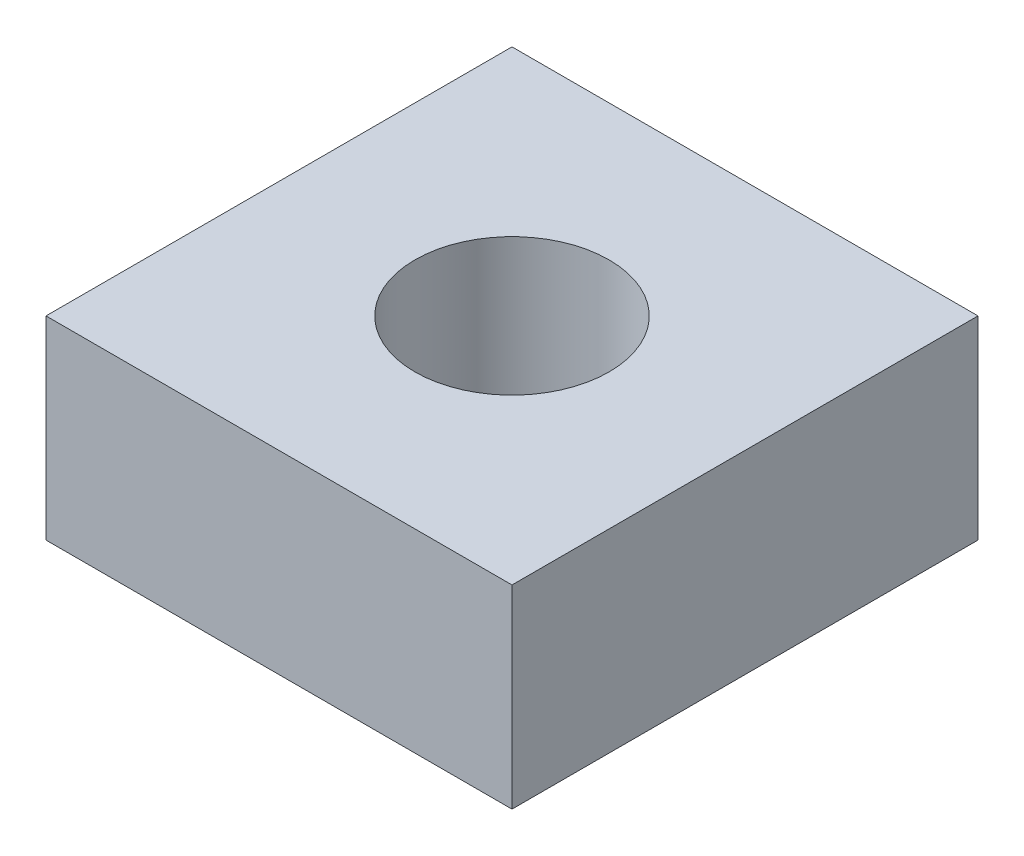
SolidWorks part; units mm, degrees
ref_plane "Front Plane" through (0, 0, 0) normal (0, 0, 1) x (1, 0, 0)
ref_plane "Top Plane" through (0, 0, 0) normal (0, 1, 0) x (1, 0, 0)
ref_plane "Right Plane" through (0, 0, 0) normal (1, 0, 0) x (0, 0, -1)
other "Center of Mass"
sketch "Sketch1" plane through (0, 0, 0) normal (0, 1, 0) x (1, 0, 0)
  line L1 (-60, 60) -> (60, 60)
  line L2 (-60, 60) -> (-60, -60)
  line L3 (-60, -60) -> (60, -60)
  line L4 (60, 60) -> (60, -60)
  line L5 (-60, 60) -> (60, -60) construction
  line L6 (-60, -60) -> (60, 60) construction
  circle A1 centre (0, 0) radius 25
  dimension "D1" = 120
  dimension "D2" = 50
  dimension "D3" = 120
extrude "Boss-Extrude1" add sketch "Sketch1" against normal blind 50
ref_axis "End_Effector_Axis" through (0, 1.25, 0) along (0, -1, 0)
